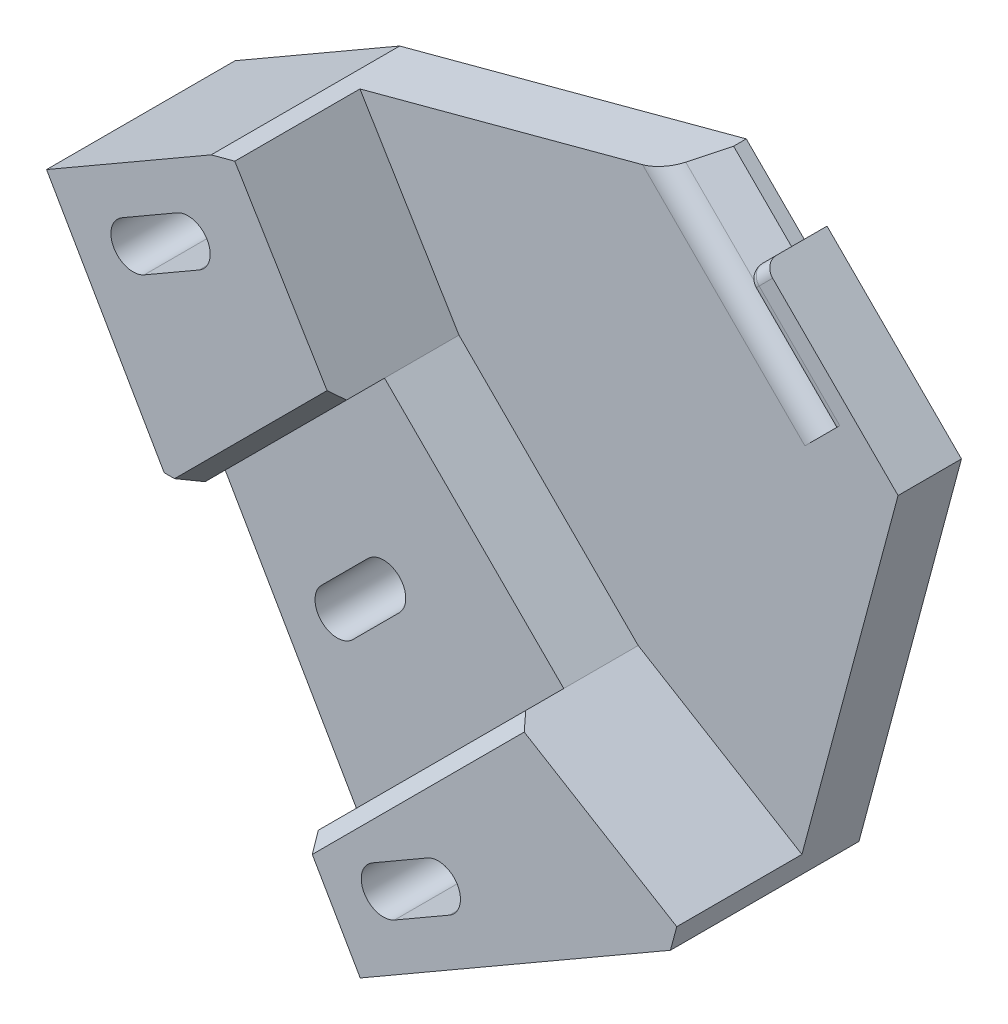
SolidWorks part; units mm, degrees
ref_plane "Front Plane" through (0, 0, 0) normal (0, 0, 1) x (1, 0, 0)
ref_plane "Top Plane" through (0, 0, 0) normal (0, 1, 0) x (1, 0, 0)
ref_plane "Right Plane" through (0, 0, 0) normal (1, 0, 0) x (0, 0, -1)
sketch "Sketch1" plane through (0, 0, 0) normal (0, 0, 1) x (1, 0, 0)
  line L0 (0, 10) -> (0, 0) construction
  line L1 (0, 0) -> (10, 0) construction
  circle A0 centre (0, 0) radius 10
  dimension "D1" = 20
sketch "Sketch2" plane through (0, 0, 0) normal (0, 0, 1) x (1, 0, 0)
  line L0 (0, 0) -> (-7.0711, -7.0711) construction
  line L1 (-7.0711, -7.0711) -> (0, -14.1421) construction
  line L2 (-7.0711, -7.0711) -> (-14.1421, 0) construction
  line L3 (14.1421, 7.0711) -> (7.0711, 14.1421) construction
  line L4 (10.6066, 10.6066) -> (7.0711, 7.0711) construction
  line L5 (7.0711, 14.1421) -> (7.7782, 14.8492) construction
  line L6 (7.7782, 14.8492) -> (14.8492, 7.7782) construction
  line L7 (14.8492, 7.7782) -> (14.1421, 7.0711) construction
  line L8 (0, -14.1421) -> (20.5061, 6.364) construction
  line L9 (20.5061, 6.364) -> (6.364, 20.5061)
  line L10 (6.364, 20.5061) -> (-14.1421, 0) construction
  line L11 (31.6334, -98.6332) -> (-88.3666, 109.2129) construction
  line L12 (25.1383, -102.3832) -> (-94.8617, 105.4629) construction
  line L13 (-81.8714, 112.9629) -> (38.1286, -94.8832) construction
  line L14 (31.6334, -98.6332) -> (-88.3666, 109.2129) construction
  line L15 (25.1383, -102.3832) -> (-94.8617, 105.4629) construction
  line L16 (-81.8714, 112.9629) -> (38.1286, -94.8832) construction
  line L17 (6.364, 20.5061) -> (-23.8217, 12.4179)
  line L18 (-23.8217, 12.4179) -> (-36.8121, 4.9179)
  line L19 (-36.8121, 4.9179) -> (-12.06, -37.954)
  line L20 (-12.06, -37.954) -> (12.4179, -23.8217)
  line L21 (12.4179, -23.8217) -> (20.5061, 6.364)
  line L39 (-16.0475, -16.0475) -> (-7.0711, -7.0711) construction
  circle A0 centre (51.2652, 51.2652) radius 82.5 construction
  circle A1 centre (51.2652, 51.2652) radius 82.5 construction
  circle A2 centre (0, 0) radius 10 construction
  circle A3 centre (0, 0) radius 10 construction
  dimension "D5" = 30
  dimension "D1" = 10
  dimension "D2" = 1
  dimension "D3" = 5
  dimension "D4" = 3
ref_plane "Plane1" through (0, 0, 0) normal (0.7071, -0.7071, 0) x (0, 0, -1)
sketch "Sketch3" plane through (0, 0, 0) normal (0.7071, -0.7071, 0) x (0, 0, -1)
  line L0 (0, 19) -> (0, -30.4591)
  line L1 (0, -30.4591) -> (-14.8754, -30.4591) construction
  line L2 (-14.8754, -30.4591) -> (-14.8754, 19) construction
  line L3 (-14.8754, 19) -> (0, 19) construction
  line L6 (-5, 19) -> (-5, -10)
  line L8 (-5, -10) -> (-10.8754, -10)
  line L9 (-10.8754, -10) -> (-10.8754, -30.4591)
  line L10 (-5, -10) -> (-11.8754, -10) construction
  line L11 (-11.8754, -10) -> (-11.8754, 19) construction
  line L12 (-10.2752, 19) -> (-10.2752, -10) construction
  line L13 (-6.6002, 19) -> (-6.6002, -10) construction
  line L14 (-11.8754, 4.5) -> (-10.2752, 4.5) construction
  line L15 (-6.6002, 4.5) -> (-5, 4.5) construction
  line L16 (-7.1002, 19) -> (-7.1002, -10) construction
  line L17 (0, -10) -> (-14.8754, -10) construction
  line L20 (-10.8754, -30.4591) -> (0, -30.4591)
  line L21 (-5, 19) -> (0, 19)
  dimension "D1" = 5
  dimension "D2" = 1.6002
  dimension "D3" = 0.5
  dimension "D4" = 3.175
  dimension "D5" = 1
  dimension "D6" = 4
extrude "Boss-Extrude1" add sketch "Sketch2" along normal up to vertex (14.8754 mm away) up to point (-21.5379, -21.5379, 14.8754)
sketch "Sketch4" plane through (0, 0, 14.8754) normal (0, 0, 1) x (1, 0, 0)
  line L0 (20.5061, 6.364) -> (6.364, 20.5061) construction
  line L1 (0, -14.1421) -> (-14.1421, 0)
  line L8 (12.4179, -23.8217) -> (20.5061, 6.364) construction
  line L9 (12.9172, -21.9582) -> (20.5061, 6.364)
  line L10 (0, -14.1421) -> (12.9172, -21.9582)
  line L11 (-14.1421, 0) -> (-21.9582, 12.9172)
  line L12 (6.364, 20.5061) -> (-23.8217, 12.4179) construction
  line L13 (6.364, 20.5061) -> (-21.9582, 12.9172)
  line L14 (20.5061, 6.364) -> (6.364, 20.5061)
  circle A0 centre (51.2652, 51.2652) radius 82.5 construction
  circle A1 centre (51.2652, 51.2652) radius 82.5 construction
extrude "Cut-Extrude1" cut sketch "Sketch4" against normal up to vertex (9.8754 mm away) up to point (-7.0711, -7.0711, 5)
sketch "Sketch5" plane through (0, 0, 14.8754) normal (0, 0, 1) x (1, 0, 0)
  line L0 (-16.3615, -30.5036) -> (20.5061, 6.364)
  line L1 (20.5061, 6.364) -> (6.364, 20.5061)
  line L2 (6.364, 20.5061) -> (-30.5036, -16.3615)
  line L3 (-30.5036, -16.3615) -> (-16.3615, -30.5036)
  line L4 (20.5061, 6.364) -> (6.364, 20.5061) construction
  line L5 (0, -14.1421) -> (20.5061, 6.364) construction
  line L6 (6.364, 20.5061) -> (-14.1421, 0) construction
  line L7 (-36.8121, 4.9179) -> (-12.06, -37.954) construction
extrude "Cut-Extrude3" cut sketch "Sketch5" against normal up to vertex (4 mm away) up to point (-7.0711, -7.0711, 10.8754)
sketch "Sketch6" plane through (0, 0, 0) normal (0, 0, 1) x (1, 0, 0)
  line L0 (31.6334, -98.6332) -> (-88.3666, 109.2129) construction
  line L1 (31.6334, -98.6332) -> (-88.3666, 109.2129) construction
  line L2 (25.1383, -102.3832) -> (-94.8617, 105.4629) construction
  line L3 (-81.8714, 112.9629) -> (38.1286, -94.8832) construction
  line L4 (25.1383, -102.3832) -> (-94.8617, 105.4629) construction
  line L5 (-81.8714, 112.9629) -> (38.1286, -94.8832) construction
  line L6 (-10.2299, -31.1239) -> (-5.8997, -28.6239) construction
  line L7 (-5.8997, -28.6239) -> (-25.6518, 5.5877) construction
  line L8 (-25.6518, 5.5877) -> (-29.9819, 3.0877) construction
  line L9 (-29.9819, 3.0877) -> (-10.2299, -31.1239) construction
  line L10 (-12.06, -37.954) -> (12.4179, -23.8217) construction
  line L11 (-23.8217, 12.4179) -> (-36.8121, 4.9179) construction
  line L12 (6.364, 20.5061) -> (-14.1421, 0) construction
  line L13 (0, -14.1421) -> (20.5061, 6.364) construction
  line L14 (-12.06, -37.954) -> (12.4179, -23.8217) construction
  line L15 (-23.8217, 12.4179) -> (-36.8121, 4.9179) construction
  line L16 (6.364, 20.5061) -> (-14.1421, 0) construction
  line L17 (0, -14.1421) -> (20.5061, 6.364) construction
  line L18 (-5.8997, -28.6239) -> (-3.3997, -32.954) construction
  line L19 (-25.6518, 5.5877) -> (-28.1518, 9.9179) construction
  line L20 (13.435, 13.435) -> (-21.5379, -21.5379) construction
  line L21 (20.5061, 6.364) -> (6.364, 20.5061) construction
  line L27 (-5.0247, -30.1394) -> (-9.3549, -32.6394)
  line L28 (-11.1049, -29.6083) -> (-6.7747, -27.1083)
  line L29 (-24.7768, 4.0722) -> (-29.1069, 1.5722)
  line L30 (-30.8569, 4.6033) -> (-26.5268, 7.1033)
  line L31 (-12.9799, -15.4548) -> (-16.6402, -19.115)
  line L32 (-19.115, -16.6402) -> (-15.4548, -12.9799)
  circle A0 centre (51.2652, 51.2652) radius 82.5 construction
  circle A1 centre (0, 0) radius 10 construction
  circle A2 centre (51.2652, 51.2652) radius 82.5 construction
  circle A3 centre (0, 0) radius 10 construction
  arc A4 (-5.0247, -30.1394) -> (-6.7747, -27.1083) centre (-5.8997, -28.6239) ccw
  arc A5 (-11.1049, -29.6083) -> (-9.3549, -32.6394) centre (-10.2299, -31.1239) ccw
  arc A6 (-24.7768, 4.0722) -> (-26.5268, 7.1033) centre (-25.6518, 5.5877) ccw
  arc A7 (-30.8569, 4.6033) -> (-29.1069, 1.5722) centre (-29.9819, 3.0877) ccw
  arc A8 (-12.9799, -15.4548) -> (-15.4548, -12.9799) centre (-14.2173, -14.2173) ccw
  arc A9 (-19.115, -16.6402) -> (-16.6402, -19.115) centre (-17.8776, -17.8776) ccw
  dimension "D2" = 3.5
  dimension "D1" = 5
  dimension "D3" = 5
extrude "Cut-Extrude4" cut sketch "Sketch6" along normal through all
sketch "Sketch8" plane through (0, 0, 0) normal (0.7071, -0.7071, 0) x (0, 0, -1)
  line L0 (0, 15) -> (-5, 15) construction
  line L1 (-5, 19) -> (-5, -10) construction
  line L2 (-5, 16) -> (0, 16) construction
  line L3 (0, 16) -> (0, 15) construction
  line L5 (-5, 16.0642) -> (0, 17.884)
  line L6 (-5, 19) -> (0, 19) construction
  line L7 (-5, 19) -> (0, 19) construction
  line L8 (-5, 15) -> (-1, 16.4559)
  line L9 (0, 19) -> (0, -30.4591) construction
  line L10 (0, 19) -> (0, -30.4591) construction
  line L12 (0, 19) -> (0, 16.4559) construction
  line L13 (0, 17.884) -> (0, 16.4559)
  line L14 (0, 19) -> (-5, 19) construction
  line L15 (-5, 19) -> (-5, 15) construction
  line L16 (-1, 16.4559) -> (0, 16.4559)
  line L17 (-5, 15) -> (-5, 16.0642)
  dimension "D1" = 20
  dimension "D3" = 1
  dimension "D5" = 1
extrude "Cut-Extrude6" cut sketch "Sketch8" along normal up to vertex (5 mm away) and the other way up to vertex (5 mm away) up to point (14.1421, 7.0711, 0) other way up to point (7.0711, 14.1421, 0)
chamfer "Chamfer3" distance 1 angle 45 2 edges at (-20.4282, -6.286, 14.8754) (-8.1807, -22.3229, 14.8754)
chamfer "Chamfer4" distance 2 angle 45 1 edges at (-26.7142, -12.5721, 12.3754)
sketch "Sketch11" plane through (-3.5355, 3.5355, 0) normal (0.7071, -0.7071, 0) x (0, 0, -1)
  line L0 (-5, 15) -> (-1, 16.4559) construction
  line L1 (-5, 15) -> (-1, 16.4559)
  line L2 (-1, 16.4559) -> (0, 16.4559) construction
  line L3 (-1, 16.4559) -> (0, 16.4559)
  line L4 (-5, 19) -> (0, 19) construction
  line L5 (-5, 19) -> (0, 19)
  line L6 (0, 16.4559) -> (0, 19)
  line L7 (-5, 19) -> (-5, 15)
extrude "Cut-Extrude8" cut sketch "Sketch11" against normal through all
fillet "Fillet4" radius 2 1 edges at (8.0223, 13.1909, 5)
fillet "Fillet5" radius 1 2 edges at (11.3591, 11.3591, 5) (8.467, 15.538, 2.5)
fillet "Fillet6" radius 1 2 edges at (9.3665, 16.4375, 5) (8.3997, 15.0565, 4.4226)
